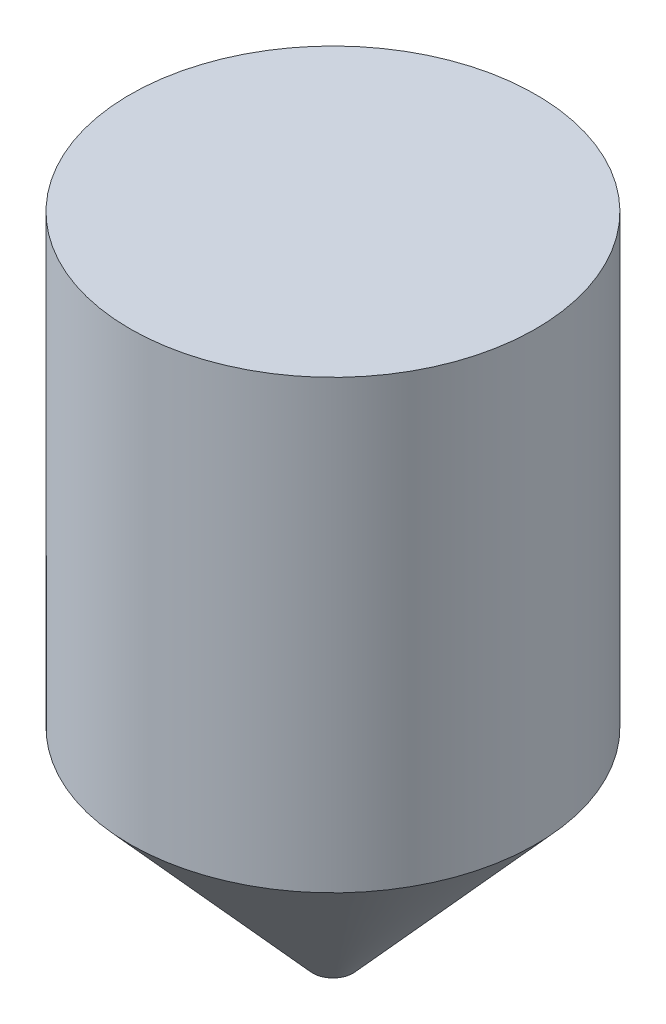
SolidWorks part; units mm, degrees
ref_plane "Front Plane" through (0, 0, 0) normal (0, 0, 1) x (1, 0, 0)
ref_plane "Top Plane" through (0, 0, 0) normal (0, 1, 0) x (1, 0, 0)
ref_plane "Right Plane" through (0, 0, 0) normal (1, 0, 0) x (0, 0, -1)
other "Configuration Table"
sketch "Sketch1" plane through (0, 0, 0) normal (0, 1, 0) x (1, 0, 0)
  circle A0 centre (0, 0) radius 1000
extrude "Boss-Extrude1" add sketch "Sketch1" along normal blind 2200 separate body
sketch "Sketch2" plane through (0, 0, 0) normal (0, 1, 0) x (1, 0, 0)
  circle A0 centre (0, 0) radius 1000
extrude "Boss-Extrude2" add sketch "Sketch2" against normal blind 1000 draft 41.998 flip side to cut separate body
